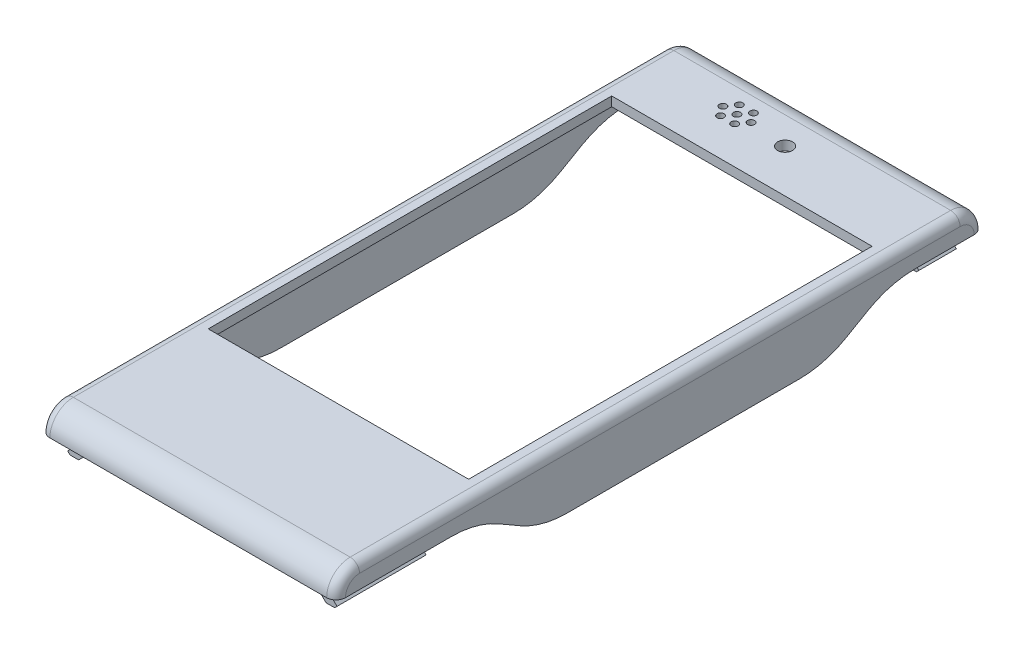
SolidWorks part; units mm, degrees
ref_plane "Front Plane" through (0, 0, 0) normal (0, 0, 1) x (1, 0, 0)
ref_plane "Top Plane" through (0, 0, 0) normal (0, 1, 0) x (1, 0, 0)
ref_plane "Right Plane" through (0, 0, 0) normal (1, 0, 0) x (0, 0, -1)
sketch "Sketch1" plane through (0, 0, 0) normal (1, 0, 0) x (0, 0, -1)
  line L0 (0, 26) -> (138, 26) construction
  line L1 (0, 0) -> (138, 0)
  line L2 (0, 0) -> (0, 31)
  line L3 (0, 31) -> (138, 31)
  line L4 (138, 0) -> (138, 31)
  line L5 (72, 0) -> (72, 31) construction
  line L6 (76, 0) -> (76, 31) construction
  line L7 (72, 15) -> (76, 15) construction
  line L8 (138, 5) -> (0, 5) construction
  line L9 (136.2933, 6) -> (139.9337, 6) construction
  line L10 (139.9337, 6) -> (139.9337, 24) construction
  line L11 (139.9337, 24) -> (136.2933, 24) construction
  line L12 (136.2933, 24) -> (136.2933, 6) construction
  line L13 (136.2933, 9) -> (141.3286, 9) construction
  line L14 (136.2933, 21) -> (141.3286, 21) construction
  line L15 (0, 26) -> (24.641, 26)
  line L16 (113.359, 23.3205) -> (108.7846, 20.6795)
  line L17 (98.7846, 18) -> (49.2154, 18)
  line L18 (39.2154, 20.6795) -> (34.641, 23.3205)
  line L21 (123.359, 26) -> (138, 26)
  arc A0 (24.641, 26) -> (34.641, 23.3205) centre (24.641, 6) cw
  arc A1 (49.2154, 18) -> (39.2154, 20.6795) centre (49.2154, 38) cw
  arc A2 (108.7846, 20.6795) -> (98.7846, 18) centre (98.7846, 38) cw
  arc A3 (113.359, 23.3205) -> (123.359, 26) centre (123.359, 6) cw
  point P23 (138.8109, 21)
  point P29 (30, 26)
  point P37 (118, 26)
  dimension "D17" = 20
  dimension "D18" = 20
  dimension "D19" = 20
  dimension "D20" = 20
  dimension "D1" = 138
  dimension "D2" = 31
  dimension "D3" = 5
  dimension "D4" = 72
  dimension "D5" = 4
  dimension "D6" = 15
  dimension "D7" = 5
  dimension "D8" = 6
  dimension "D9" = 18
  dimension "D10" = 9
  dimension "D11" = 12
  dimension "D12" = 30
  dimension "D13" = 20
  dimension "D14" = 30
  dimension "D15" = 30
  dimension "D16" = 18
extrude "Boss-Extrude1" add sketch "Sketch1" along normal blind 63 contours L16 A3 L21 L4 L3 L2 L15 A0 L18 A1 L17 A2
shell "Shell1" thickness 2
fillet "Fillet1" radius 5 2 edges at (31.5, 31, -138) (31.5, 31, 0)
fillet "Fillet2" radius 2 6 edges at (0, 29.5355, -1.4645) (0, 29.5355, -136.5355) (63, 29.5355, -1.4645) (63, 29.5355, -136.5355) (0, 31, -69) (63, 31, -69)
fillet "Fillet3" radius 3 1 edges at (31.5, 29, -136)
fillet "Fillet4" radius 3 1 edges at (31.5, 29, -2)
sketch "Sketch2" plane through (0, 31, 0) normal (0, 1, 0) x (1, 0, 0)
  line L0 (61, 133) -> (2, 133) construction
  line L1 (3.75, 118) -> (59.25, 118)
  line L2 (3.75, 118) -> (3.75, 32)
  line L3 (3.75, 32) -> (59.25, 32)
  line L4 (59.25, 118) -> (59.25, 32)
  line L5 (2, 133) -> (2, 5) construction
  dimension "D1" = 55.5
  dimension "D2" = 86
  dimension "D3" = 15
  dimension "D4" = 1.75
extrude "Cut-Extrude1" cut sketch "Sketch2" against normal through all
sketch "Sketch6" plane through (0, 29, 0) normal (0, -1, 0) x (1, 0, 0)
  line L0 (58.7, -3) -> (58.7, -22)
  line L2 (61, -2) -> (61, -24.641) construction
  line L3 (56.7, -3) -> (56.7, -22)
  line L4 (56.7, -22) -> (58.7, -22)
  line L5 (58.7, -3) -> (56.7, -3)
  line L6 (61, -5) -> (61, -28) construction
  line L7 (61, -5) -> (61, -133) construction
  line L8 (61, -28) -> (56.7, -28) construction
  dimension "D1" = 19
  dimension "D2" = 2.3
  dimension "D3" = 2
  dimension "D4" = 23
  dimension "D5" = 6
extrude "Boss-Extrude2" add sketch "Sketch6" along normal blind 5
sketch "Sketch9" plane through (0, 0, -22) normal (0, 0, -1) x (-1, 0, 0)
  line L0 (-58.7, 24) -> (-60.7, 22)
  line L7 (-58.7, 24) -> (-58.7, 29) construction
  line L8 (-56.7, 29) -> (-58.7, 29)
  line L9 (-58.7, 29) -> (-58.7, 24)
  line L10 (-58.7, 24) -> (-56.7, 24)
  line L11 (-56.7, 24) -> (-56.7, 29)
  line L14 (-58.7, 24) -> (-56.7, 24)
  line L16 (-60.7, 22) -> (-58.7, 22)
  line L18 (-56.7, 24) -> (-56.7, 23.1716)
  line L19 (-56.7, 23.1716) -> (-57.8716, 22)
  line L20 (-58.7, 22) -> (-57.8716, 22)
  dimension "D1" = 135
  dimension "D2" = 2
  dimension "D3" = 2
  dimension "D5" = 2
  dimension "D4" = 0
extrude "Boss-Extrude4" add sketch "Sketch9" against normal blind 19
ref_plane "Plane2" through (31.5, 0, 0) normal (1, 0, 0) x (0, 0, -1)
ref_plane "Plane3" through (0, 0, 7) normal (0, 0, 1) x (1, 0, 0)
chamfer "Chamfer4" distance 1 angle 45 1 edges at (60.7, 22, -12.5)
mirror "Mirror2" about plane through (31.5, 0, 0) normal (1, 0, 0) of "Boss-Extrude2", "Boss-Extrude4", "Chamfer4"
fillet "Fillet5" radius 2 1 edges at (6.3, 29, -13.5)
sketch "Sketch14" plane through (0, 29, 0) normal (0, -1, 0) x (1, 0, 0)
  line L1 (56.7, -127) -> (58.7, -127)
  line L2 (56.7, -127) -> (56.7, -135)
  line L3 (56.7, -135) -> (58.7, -135)
  line L4 (58.7, -127) -> (58.7, -135)
  line L5 (61, -123.359) -> (61, -136) construction
  line L6 (61, -133) -> (61, -125) construction
  line L7 (61, -5) -> (61, -133) construction
  line L8 (61, -125) -> (56.8, -125) construction
  dimension "D1" = 8
  dimension "D2" = 2
  dimension "D3" = 2.3
  dimension "D4" = 8
  dimension "D5" = 2
extrude "Boss-Extrude5" add sketch "Sketch14" along normal blind 5
sketch "Sketch15" plane through (0, 0, -135) normal (0, 0, -1) x (-1, 0, 0)
  line L0 (-58.7, 24) -> (-60.7, 22)
  line L3 (-58.7, 24) -> (-58.7, 28.2361) construction
  line L4 (-56.7, 24) -> (-56.7, 23.1716)
  line L5 (-56.7, 23.1716) -> (-57.8716, 22)
  line L6 (-57.8716, 22) -> (-60.7, 22)
  line L8 (-56.7, 24) -> (-56.7, 28.2361)
  line L9 (-56.7, 28.2361) -> (-58.7, 28.2361)
  line L10 (-58.7, 28.2361) -> (-58.7, 24)
  line L11 (-58.7, 24) -> (-56.7, 24)
  line L15 (-58.7, 24) -> (-56.7, 24)
  line L16 (-56.7, 28.2361) -> (-58.7, 28.2361)
  line M11 (-58.7, 24) -> (-56.7, 24)
  dimension "D1" = 135
  dimension "D2" = 2
  dimension "D3" = 2
  dimension "D4" = 0
extrude "Boss-Extrude6" add sketch "Sketch15" against normal blind 8 contours L6 L5 L4 L0 M11
sketch "Sketch19" plane through (0, 31, 0) normal (0, 1, 0) x (1, 0, 0)
  line L0 (3.75, 118) -> (3.75, 125) construction
  line L1 (3.75, 125) -> (59.25, 125) construction
  line L2 (59.25, 125) -> (59.25, 118) construction
  line L3 (3.75, 118) -> (3.75, 32) construction
  line L6 (59.25, 32) -> (59.25, 118) construction
  line L7 (31.5, 133) -> (31.5, 125) construction
  line L8 (61, 133) -> (2, 133) construction
  line L10 (2, 122.9254) -> (16, 122.9254) construction
  line L11 (2, 133) -> (2, 5) construction
  line L12 (16, 122.9254) -> (16, 133) construction
  circle A0 centre (31.5, 127.2) radius 1.6
  dimension "D2" = 3.2
  dimension "D3" = 2.2
  dimension "D1" = 7
  dimension "D4" = 14
sketch "Sketch20" plane through (0, 31, 0) normal (0, 1, 0) x (1, 0, 0)
  line L0 (3.75, 125) -> (59.25, 125) construction
  line L1 (16, 122.9254) -> (16, 133) construction
  circle A0 centre (20.5, 127.95) radius 0.75
  circle A1 centre (17.5, 127.95) radius 0.75
  circle A2 centre (23.5, 127.95) radius 0.75
  circle A3 centre (19, 129.95) radius 0.75
  circle A4 centre (22, 129.95) radius 0.75
  circle A5 centre (19, 125.95) radius 0.75
  circle A6 centre (22, 125.95) radius 0.75
  dimension "D1" = 1.5
  dimension "D2" = 1.5
  dimension "D3" = 1.5
  dimension "D4" = 3
  dimension "D5" = 3
  dimension "D6" = 1.5
  dimension "D7" = 1.5
  dimension "D8" = 3
  dimension "D9" = 1.5
  dimension "D10" = 1.5
  dimension "D11" = 3
  dimension "D12" = 1.5
  dimension "D13" = 2
  dimension "D14" = 2
  dimension "D15" = 1.5
  dimension "D17" = 3
  dimension "D16" = 0.95
extrude "Cut-Extrude2" cut sketch "Sketch19" against normal blind 9
extrude "Cut-Extrude3" cut sketch "Sketch20" against normal blind 9
chamfer "Chamfer5" distance 1 angle 45 1 edges at (60.7, 22, -131)
mirror "Mirror4" about plane through (31.5, 0, 0) normal (1, 0, 0) of "Chamfer5", "Boss-Extrude6", "Boss-Extrude5"
fillet "Fillet6" radius 2 1 edges at (4.3, 29, -13.5)
fillet "Fillet7" radius 2 1 edges at (56.7, 29, -13.5)
fillet "Fillet8" radius 2 1 edges at (58.7, 29, -13.5)
fillet "Fillet9" radius 2 2 edges at (6.3, 28.8025, -134.0705) (6.3, 29, -130)
fillet "Fillet10" radius 2 1 edges at (4.3, 29, -130)
fillet "Fillet11" radius 2 1 edges at (56.7, 29, -130)
fillet "Fillet12" radius 2 1 edges at (58.7, 29, -130)
sketch "Sketch25" plane through (0, 29, 0) normal (0, -1, 0) x (1, 0, 0)
  line L0 (2.3, -127) -> (8.3, -127)
  line L1 (8.3, -127) -> (8.3, -128)
  line L2 (8.3, -127) -> (8.3, -133) construction
  line L3 (8.3, -128) -> (2.3, -128)
  line L4 (2.3, -133) -> (2.3, -127) construction
  line L5 (2.3, -128) -> (2.3, -127)
  dimension "D1" = 1
extrude "Cut-Extrude4" cut sketch "Sketch25" along normal blind 10
